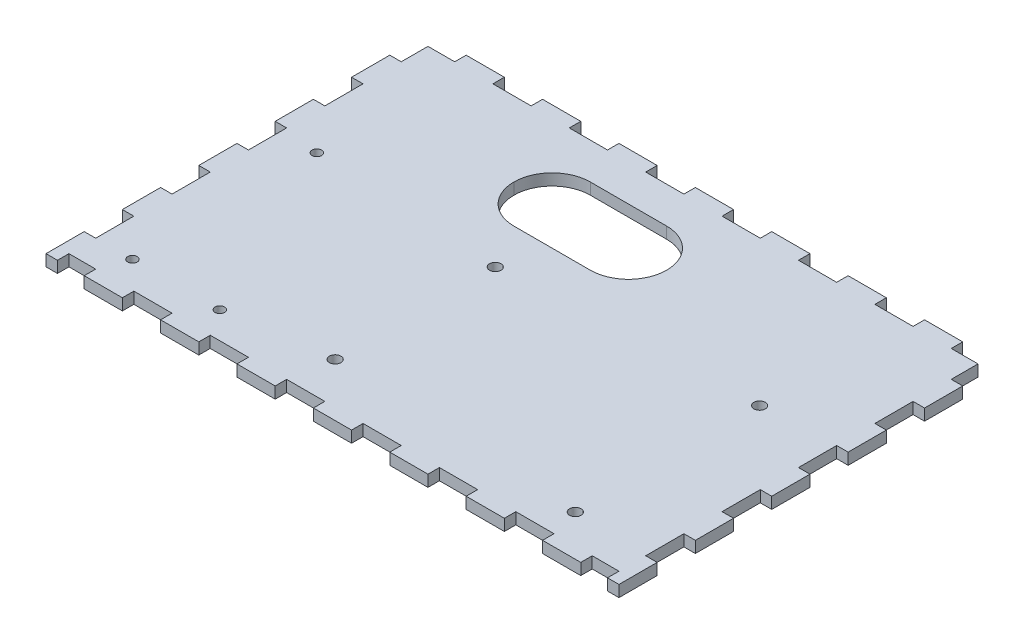
SolidWorks part; units mm, degrees
ref_plane "Front Plane" through (0, 0, 0) normal (0, 0, 1) x (1, 0, 0)
ref_plane "Top Plane" through (0, 0, 0) normal (0, 1, 0) x (1, 0, 0)
ref_plane "Right Plane" through (0, 0, 0) normal (1, 0, 0) x (0, 0, -1)
sketch "Sketch1" plane through (0, 0, 0) normal (0, 1, 0) x (1, 0, 0)
  line L1 (-75, -50) -> (75, -50)
  line L2 (-75, -50) -> (-75, 50)
  line L3 (-75, 50) -> (75, 50)
  line L4 (75, -50) -> (75, 50)
  line L5 (-75, -50) -> (75, 50) construction
  line L6 (-75, 50) -> (75, -50) construction
  point P0 (0, 0)
  dimension "D1" = 150
  dimension "D2" = 100
extrude "Boss-Extrude1" add sketch "Sketch1" along normal blind 3
sketch "Sketch2" plane through (0, 3, 0) normal (0, 1, 0) x (1, 0, 0)
  line L0 (-75, -50) -> (75, -50) construction
  line L1 (-75, -50) -> (-65, -50)
  line L2 (-75, -50) -> (-75, -47)
  line L3 (-75, -47) -> (-65, -47)
  line L4 (-65, -50) -> (-65, -47)
  dimension "D2" = 10
  dimension "D3" = 3
extrude "Cut-Extrude2" cut sketch "Sketch2" against normal through all
pattern_linear "LPattern1" count 8 spacing 20 along (1, 0, 0) of "Cut-Extrude2"
mirror "Mirror1" about plane through (0, 0, 0) normal (0, 0, 1) of "LPattern1"
sketch "Sketch3" plane through (0, 3, 0) normal (0, 1, 0) x (1, 0, 0)
  line L0 (-75, 47) -> (-75, -47) construction
  line L1 (-75, -40) -> (-72, -40)
  line L2 (-75, -40) -> (-75, -30)
  line L3 (-75, -30) -> (-72, -30)
  line L4 (-72, -40) -> (-72, -30)
  line L6 (-65, -50) -> (-55, -50) construction
  dimension "D1" = 10
  dimension "D2" = 10
  dimension "D3" = 3
extrude "Cut-Extrude3" cut sketch "Sketch3" against normal through all
pattern_linear "LPattern2" count 5 spacing 20 along (0, 0, -1) of "Cut-Extrude3"
mirror "Mirror2" about plane through (0, 0, 0) normal (1, 0, 0) of "LPattern2"
sketch "Sketch4" plane through (0, 3, 0) normal (0, 1, 0) x (1, 0, 0)
  line L0 (-75, 40) -> (-75, 30) construction
  line L1 (-30, 37.5) -> (10, 37.5)
  line L2 (-30, 37.5) -> (-30, 17.5)
  line L3 (-30, 17.5) -> (10, 17.5)
  line L4 (10, 37.5) -> (10, 17.5)
  line L5 (-35, 50) -> (-45, 50) construction
  dimension "D1" = 45
  dimension "D2" = 12.5
  dimension "D3" = 20
  dimension "D4" = 40
extrude "Cut-Extrude4" cut sketch "Sketch4" against normal through all
fillet "Fillet1" radius 10 4 edges at (10, 1.5, -17.5) (10, 1.5, -37.5) (-30, 1.5, -37.5) (-30, 1.5, -17.5)
sketch "Sketch5" plane through (0, 0, 47) normal (0, 0, 1) x (1, 0, 0)
  line L0 (75, 0) -> (65, 0) construction
  line L1 (75, 3) -> (72, 3)
  line L2 (75, 3) -> (75, 0)
  line L3 (75, 0) -> (72, 0)
  line L4 (72, 3) -> (72, 0)
  line L5 (72, 3) -> (72, -7) construction
extrude "Boss-Extrude2" add sketch "Sketch5" along normal blind 3
mirror "Mirror3" about plane through (0, 0, 0) normal (1, 0, 0) of "Boss-Extrude2"
sketch "Sketch6" plane through (0, 3, 0) normal (0, 1, 0) x (1, 0, 0)
  circle A0 centre (-13.1677, -36.1252) radius 1.5
  circle A1 centre (-13.1677, 5.7848) radius 1.5
  circle A2 centre (52.8723, 8.9598) radius 1.5
  circle A3 centre (52.8723, -39.3002) radius 1.5
  circle A4 centre (-39.54, -39.96) radius 1.25
  circle A5 centre (-62.4, -39.96) radius 1.25
  circle A6 centre (-62.4, 8.3) radius 1.25
extrude "Cut-Extrude5" cut sketch "Sketch6" against normal through all
